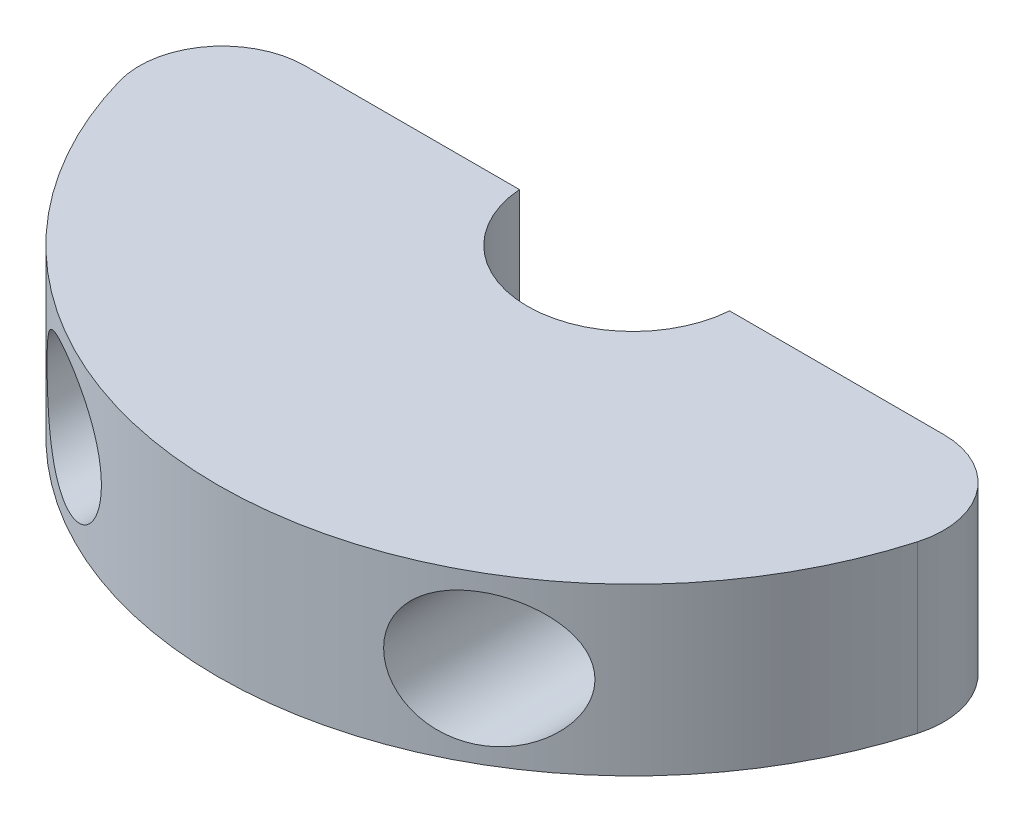
SolidWorks part; units mm, degrees
material "Nylon 101"
ref_plane "Front" through (0, 0, 0) normal (0, 0, 1) x (1, 0, 0)
ref_plane "Top" through (0, 0, 0) normal (0, 1, 0) x (1, 0, 0)
ref_plane "Right" through (0, 0, 0) normal (1, 0, 0) x (0, 0, -1)
sketch "Sketch1" plane through (0, 0, 0) normal (0, 1, 0) x (1, 0, 0)
  line L0 (-25, -50) -> (25, -50) construction
  line L1 (-15, 37.5) -> (15, 37.5) construction
  line L2 (0, -50) -> (0, 50) construction
  line L3 (-25, -50) -> (-25, 50)
  line L4 (25, -50) -> (25, 50)
  line L5 (25, 0) -> (0, 0) construction
  line L6 (25, 17) -> (97.2, 17)
  line L7 (25, 17) -> (25, -17)
  line L8 (25, -17) -> (97.2, -17)
  line L9 (97.2, 17) -> (97.2, -17)
  line L10 (-15, 37.5) -> (-15, -37.5) construction
  line L11 (-15, -37.5) -> (15, -37.5) construction
  line L12 (15, 37.5) -> (15, -37.5) construction
  line L13 (-25, -50.5) -> (25, -50.5)
  line L14 (-25, -49.5) -> (25, -49.5)
  line L15 (-25, 50.5) -> (25, 50.5)
  line L16 (-25, 49.5) -> (25, 49.5)
  circle A0 centre (0, 50) radius 6.35
  circle A1 centre (0, -50) radius 6.35
  arc A2 (-25, -50) -> (25, -50) centre (0, -50) ccw
  arc A3 (25, 50) -> (-25, 50) centre (0, 50) ccw
  circle A6 centre (-15, 37.5) radius 2.5
  circle A7 centre (-15, -37.5) radius 2.5
  circle A8 centre (15, -37.5) radius 2.5
  circle A9 centre (15, 37.5) radius 2.5
  point P8 (0, 0)
  point P24 (0, -37.5)
  dimension "D2" = 12.7
  dimension "D5" = 25
  dimension "D1" = 5
  dimension "D3" = 100
  dimension "D4" = 12.5
  dimension "D6" = 12.5
  dimension "D7" = 34
  dimension "D8" = 72.2
  dimension "D9" = 30
  dimension "D10" = 0.5
  dimension "D11" = 0.5
extrude "Boss-Extrude1" add sketch "Sketch1" along normal blind 10 contours L13 A2 A1 region at (0, 0, 61.3823)
fillet "Fillet1" radius 5 2 edges at (-24.995, 5, 50.5) (24.995, 5, 50.5)
sketch "Sketch2" plane through (0, 0, 50.5) normal (0, 0, -1) x (-1, 0, 0)
  line L0 (-12.5, 10) -> (-12.5, 0) construction
  line L1 (-6.3303, 10) -> (-19.2289, 10) construction
  line L2 (-6.3303, 0) -> (-19.2289, 0) construction
  line L3 (12.5, 10) -> (12.5, 0) construction
  line L4 (19.2289, 10) -> (6.3303, 10) construction
  line L5 (19.2289, 0) -> (6.3303, 0) construction
  line L6 (0, 0) -> (0, 2.7242) construction
  line L7 (-6.3303, 0) -> (6.3303, 0) construction
  circle A0 centre (-12.5, 5) radius 1.5
  circle A1 centre (12.5, 5) radius 1.5
  circle A2 centre (-12.5, 5) radius 4
  circle A3 centre (12.5, 5) radius 4
  dimension "D1" = 3
  dimension "D3" = 8
  dimension "D2" = 12.5
extrude "Cut-Extrude1" cut sketch "Sketch2" against normal through all contours A0 | A1 region at (12.5, 5, 50.5) region at (-12.5, 5, 50.5)
extrude "Cut-Extrude2" cut sketch "Sketch2<3>" against normal through all from offset 10 contours A2 A0 | A3 A1 region at (16.3869, 5, 50.5) region at (-8.6131, 5, 50.5) offset against normal yes
sketch "Sketch2<3>" plane through (0, 0, 50.5) normal (0, 0, -1) x (-1, 0, 0) same geometry as "Sketch2"
